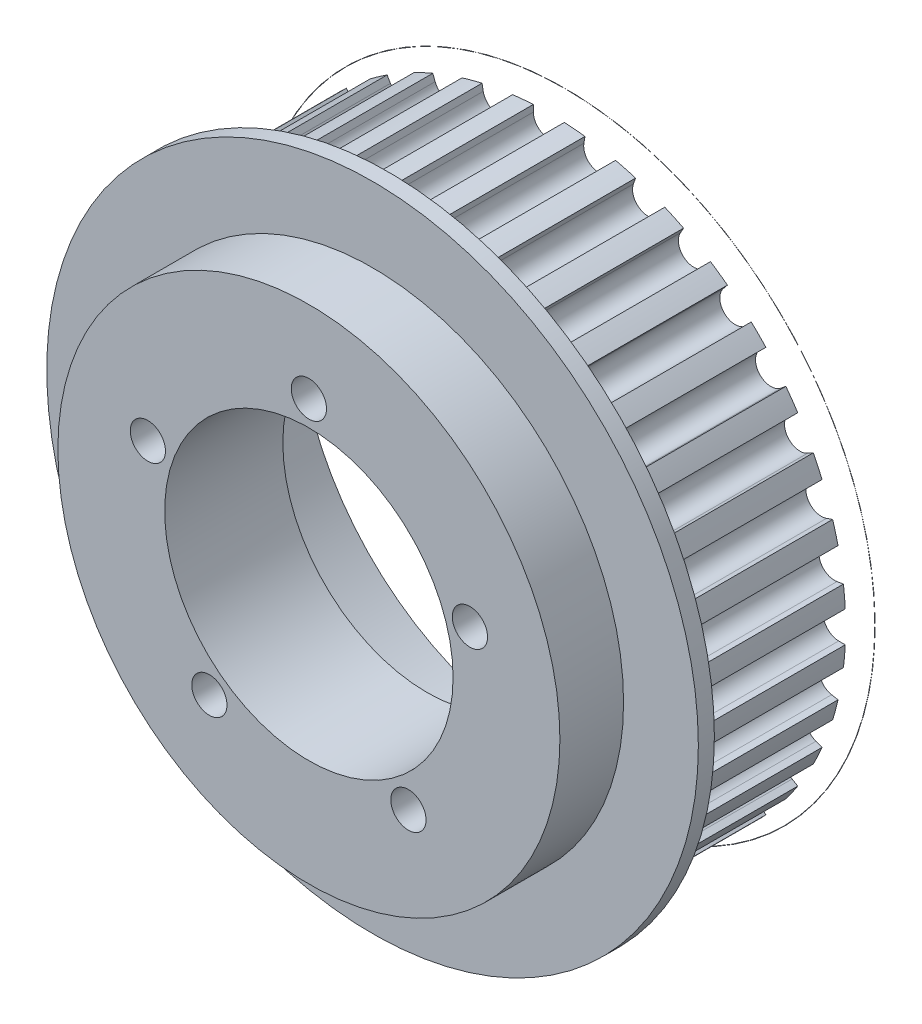
SolidWorks part; units mm, degrees
material "6061 Alloy"
ref_plane "Front Plane" through (0, 0, 0) normal (0, 0, 1) x (1, 0, 0)
ref_plane "Top Plane" through (0, 0, 0) normal (0, 1, 0) x (1, 0, 0)
ref_plane "Right Plane" through (0, 0, 0) normal (1, 0, 0) x (0, 0, -1)
sketch "Sketch1" plane through (0, 0, 0) normal (0, 0, 1) x (1, 0, 0)
  line L3 (-1.4732, 29.5146) -> (1.4732, 29.5146) construction
  line L4 (0, 0) -> (0, 25.7046) construction
  line L5 (0, 25.7046) -> (0, 27.7874) construction
  line L6 (-1.4479, 27.1372) -> (-1.4732, 29.5146)
  line L7 (1.4479, 27.1372) -> (1.4732, 29.5146)
  line L8 (0, 27.7874) -> (0, 29.5146) construction
  circle A0 centre (0, 0) radius 28.651 construction
  circle A1 centre (0, 0) radius 30.23 construction
  arc A3 (-1.4479, 27.1372) -> (1.4479, 27.1372) centre (0, 27.1526) ccw
  point P11 (0, 28.651)
  point P13 (0, 30.23)
  dimension "D3" = 1.448
  dimension "D1" = 2.9464
  dimension "D2" = 3.81
sketch "Sketch2" plane through (0, 0, 0) normal (1, 0, 0) x (0, 0, -1)
  line L0 (-17.02, 6.75) -> (17.02, 6.75)
  line L2 (-4.32, 22.86) -> (-17.02, 22.86)
  line L4 (-4.32, 30.23) -> (17.02, 30.23) construction
  line L5 (6.35, 30.23) -> (6.35, 27.7874) construction
  line L6 (-1.905, 27.7874) -> (14.605, 27.7874)
  line L7 (14.605, 27.7874) -> (14.605, 29.0087)
  line L8 (14.605, 29.0087) -> (14.605, 30.23) construction
  line L9 (17.02, 30.23) -> (17.02, 6.75)
  line L10 (-17.02, 0) -> (17.02, 0) construction
  line L11 (-17.02, 22.86) -> (-17.02, 6.75)
  line L12 (-4.32, 22.86) -> (-4.32, 30.23)
  line L13 (17.02, 30.23) -> (15.8125, 30.23)
  line L14 (15.8125, 30.23) -> (14.605, 30.23) construction
  line L15 (-1.905, 27.7874) -> (-1.905, 29.0087)
  line L16 (-1.905, 29.0087) -> (-1.905, 30.23) construction
  line L17 (-1.905, 30.23) -> (-3.1125, 30.23) construction
  line L18 (-3.1125, 30.23) -> (-4.32, 30.23)
  arc A0 (15.8125, 30.23) -> (14.605, 29.0087) centre (15.8125, 29.0224) ccw
  arc A1 (-1.905, 29.0087) -> (-3.1125, 30.23) centre (-3.1264, 29.0087) ccw
  point P25 (17.02, 0)
  point P26 (-4.32, 0)
  dimension "ID" = 13.5
  dimension "Hub Dia" = 45.72
  dimension "Outside Width" = 21.34
  dimension "Inside Width" = 16.51
  dimension "D2" = 60.46
revolve "Revolve1" add sketch "Sketch2" angle 360 mid plane about L10
sketch "Sketch3" plane through (0, 0, 0) normal (0, 0, 1) x (1, 0, 0)
  line L3 (-1.4479, 27.1372) -> (-1.4732, 29.5146) construction
  line L4 (1.4479, 27.1372) -> (1.4732, 29.5146) construction
  line L5 (-1.4479, 27.1372) -> (-1.4544, 27.7493)
  line L6 (1.4479, 27.1372) -> (1.4544, 27.7493)
  circle A2 centre (0, 0) radius 27.7874 construction
  arc A3 (-1.4479, 27.1372) -> (1.4479, 27.1372) centre (0, 27.1526) ccw construction
  arc A4 (-1.4479, 27.1372) -> (1.4479, 27.1372) centre (0, 27.1526) ccw
  arc A5 (1.4544, 27.7493) -> (-1.4544, 27.7493) centre (0, 0) ccw
extrude "Cut-Extrude1" cut sketch "Sketch3" against normal up to vertex (14.605 mm away) from vertex at 1.905 starting at point (0, 27.7874, 1.905)
pattern_circular "CirPattern1" count 36 over 360 about axis through (0, 0, 0) along (0, 0, 1) of "Cut-Extrude1"
sketch "Sketch4" plane through (0, 0, 0) normal (1, 0, 0) x (0, 0, -1)
  line L0 (15.8125, -30.23) -> (17.02, -30.23) construction
  line L1 (17.02, 30.23) -> (14.605, 30.23)
  line L2 (17.02, 30.23) -> (17.02, -30.23)
  line L3 (17.02, -30.23) -> (14.605, -30.23)
  line L4 (14.605, 30.23) -> (14.605, -30.23)
  line L5 (17.02, -30.23) -> (17.02, 30.23) construction
  line L6 (14.605, 29.0087) -> (14.605, -29.0087) construction
  line L7 (-4.32, 30.23) -> (-4.32, -30.23) construction
  line L8 (-4.32, 30.23) -> (-1.905, 30.23)
  line L9 (-4.32, 30.23) -> (-4.32, -30.23)
  line L10 (-4.32, -30.23) -> (-1.905, -30.23)
  line L11 (-1.905, 30.23) -> (-1.905, -30.23)
  line L12 (-1.905, -23.3044) -> (-1.905, -22.1921) construction
  line L13 (-17.02, 22.86) -> (-17.02, -22.86) construction
  line L14 (-17.02, 22.86) -> (-4.32, 22.86)
  line L15 (-17.02, 22.86) -> (-17.02, -22.86)
  line L16 (-17.02, -22.86) -> (-4.32, -22.86)
  line L17 (-4.32, 22.86) -> (-4.32, -22.86)
  line L18 (-4.32, 22.86) -> (-4.32, -22.86) construction
  line L19 (0, 0) -> (-17.02, 0) construction
  line L20 (-17.02, 0) -> (17.02, 0)
  dimension "D1" = 45.72
revolve "Cut-Revolve2" cut sketch "Sketch4" angle 360 about L19
sketch "Sketch5" plane through (0, 0, -14.605) normal (0, 0, -1) x (-1, 0, 0)
  line L72 (26.4735, 6.1382) -> (27.0752, 6.2509)
  line L73 (26.5733, 8.1241) -> (25.9958, 7.9209)
  line L74 (25.0054, 10.6421) -> (25.5784, 10.8575)
  line L75 (24.7588, 12.6151) -> (24.2255, 12.3147)
  line L76 (22.7775, 14.8225) -> (23.3044, 15.1342)
  line L77 (22.1921, 16.7228) -> (21.719, 16.3343)
  line L78 (19.8576, 18.5526) -> (20.3223, 18.9511)
  line L79 (18.9511, 20.3223) -> (18.5526, 19.8576)
  line L80 (16.3343, 21.719) -> (16.7228, 22.1921)
  line L81 (15.1342, 23.3044) -> (14.8225, 22.7775)
  line L82 (12.3147, 24.2255) -> (12.6151, 24.7588)
  line L83 (10.8575, 25.5784) -> (10.6421, 25.0054)
  line L84 (7.9209, 25.9958) -> (8.1241, 26.5733)
  line L85 (6.2509, 27.0752) -> (6.1382, 26.4735)
  line L86 (3.2864, 26.9764) -> (3.3863, 27.5803)
  line L87 (1.4544, 27.7493) -> (1.4479, 27.1372)
  line L88 (-1.4479, 27.1372) -> (-1.4544, 27.7493)
  line L89 (-3.3863, 27.5803) -> (-3.2864, 26.9764)
  line L90 (-6.1382, 26.4735) -> (-6.2509, 27.0752)
  line L91 (-8.1241, 26.5733) -> (-7.9209, 25.9958)
  line L92 (-10.6421, 25.0054) -> (-10.8575, 25.5784)
  line L93 (-12.6151, 24.7588) -> (-12.3147, 24.2255)
  line L94 (-14.8225, 22.7775) -> (-15.1342, 23.3044)
  line L95 (-16.7228, 22.1921) -> (-16.3343, 21.719)
  line L96 (-18.5526, 19.8576) -> (-18.9511, 20.3223)
  line L97 (-20.3223, 18.9511) -> (-19.8576, 18.5526)
  line L98 (-21.719, 16.3343) -> (-22.1921, 16.7228)
  line L99 (-23.3044, 15.1342) -> (-22.7775, 14.8225)
  line L100 (-24.2255, 12.3147) -> (-24.7588, 12.6151)
  line L101 (-25.5784, 10.8575) -> (-25.0054, 10.6421)
  line L102 (-25.9958, 7.9209) -> (-26.5733, 8.1241)
  line L103 (-27.0752, 6.2509) -> (-26.4735, 6.1382)
  line L104 (-26.9764, 3.2864) -> (-27.5803, 3.3863)
  line L105 (-27.7493, 1.4544) -> (-27.1372, 1.4479)
  line L106 (-27.1372, -1.4479) -> (-27.7493, -1.4544)
  line L107 (-27.5803, -3.3863) -> (-26.9764, -3.2864)
  line L108 (-26.4735, -6.1382) -> (-27.0752, -6.2509)
  line L109 (-26.5733, -8.1241) -> (-25.9958, -7.9209)
  line L110 (-25.0054, -10.6421) -> (-25.5784, -10.8575)
  line L111 (-24.7588, -12.6151) -> (-24.2255, -12.3147)
  line L112 (-22.7775, -14.8225) -> (-23.3044, -15.1342)
  line L113 (-22.1921, -16.7228) -> (-21.719, -16.3343)
  line L114 (-19.8576, -18.5526) -> (-20.3223, -18.9511)
  line L115 (-18.9511, -20.3223) -> (-18.5526, -19.8576)
  line L116 (-16.3343, -21.719) -> (-16.7228, -22.1921)
  line L117 (-15.1342, -23.3044) -> (-14.8225, -22.7775)
  line L118 (-12.3147, -24.2255) -> (-12.6151, -24.7588)
  line L119 (-10.8575, -25.5784) -> (-10.6421, -25.0054)
  line L120 (-7.9209, -25.9958) -> (-8.1241, -26.5733)
  line L121 (-6.2509, -27.0752) -> (-6.1382, -26.4735)
  line L122 (-3.2864, -26.9764) -> (-3.3863, -27.5803)
  line L123 (-1.4544, -27.7493) -> (-1.4479, -27.1372)
  line L124 (1.4479, -27.1372) -> (1.4544, -27.7493)
  line L125 (3.3863, -27.5803) -> (3.2864, -26.9764)
  line L126 (6.1382, -26.4735) -> (6.2509, -27.0752)
  line L127 (8.1241, -26.5733) -> (7.9209, -25.9958)
  line L128 (10.6421, -25.0054) -> (10.8575, -25.5784)
  line L129 (12.6151, -24.7588) -> (12.3147, -24.2255)
  line L130 (14.8225, -22.7775) -> (15.1342, -23.3044)
  line L131 (16.7228, -22.1921) -> (16.3343, -21.719)
  line L132 (18.5526, -19.8576) -> (18.9511, -20.3223)
  line L133 (20.3223, -18.9511) -> (19.8576, -18.5526)
  line L134 (21.719, -16.3343) -> (22.1921, -16.7228)
  line L135 (23.3044, -15.1342) -> (22.7775, -14.8225)
  line L136 (24.2255, -12.3147) -> (24.7588, -12.6151)
  line L137 (25.5784, -10.8575) -> (25.0054, -10.6421)
  line L138 (25.9958, -7.9209) -> (26.5733, -8.1241)
  line L139 (27.0752, -6.2509) -> (26.4735, -6.1382)
  line L140 (26.9764, -3.2864) -> (27.5803, -3.3863)
  line L141 (27.7493, -1.4544) -> (27.1372, -1.4479)
  line L142 (27.1372, 1.4479) -> (27.7493, 1.4544)
  line L143 (27.5803, 3.3863) -> (26.9764, 3.2864)
  line L144 (26.4735, 6.1382) -> (27.0752, 6.2509)
  line L145 (26.5733, 8.1241) -> (25.9958, 7.9209)
  line L146 (25.0054, 10.6421) -> (25.5784, 10.8575)
  line L147 (24.7588, 12.6151) -> (24.2255, 12.3147)
  line L148 (22.7775, 14.8225) -> (23.3044, 15.1342)
  line L149 (22.1921, 16.7228) -> (21.719, 16.3343)
  line L150 (19.8576, 18.5526) -> (20.3223, 18.9511)
  line L151 (18.9511, 20.3223) -> (18.5526, 19.8576)
  line L152 (16.3343, 21.719) -> (16.7228, 22.1921)
  line L153 (15.1342, 23.3044) -> (14.8225, 22.7775)
  line L154 (12.3147, 24.2255) -> (12.6151, 24.7588)
  line L155 (10.8575, 25.5784) -> (10.6421, 25.0054)
  line L156 (7.9209, 25.9958) -> (8.1241, 26.5733)
  line L157 (6.2509, 27.0752) -> (6.1382, 26.4735)
  line L158 (3.2864, 26.9764) -> (3.3863, 27.5803)
  line L159 (1.4544, 27.7493) -> (1.4479, 27.1372)
  line L160 (-1.4479, 27.1372) -> (-1.4544, 27.7493)
  line L161 (-3.3863, 27.5803) -> (-3.2864, 26.9764)
  line L162 (-6.1382, 26.4735) -> (-6.2509, 27.0752)
  line L163 (-8.1241, 26.5733) -> (-7.9209, 25.9958)
  line L164 (-10.6421, 25.0054) -> (-10.8575, 25.5784)
  line L165 (-12.6151, 24.7588) -> (-12.3147, 24.2255)
  line L166 (-14.8225, 22.7775) -> (-15.1342, 23.3044)
  line L167 (-16.7228, 22.1921) -> (-16.3343, 21.719)
  line L168 (-18.5526, 19.8576) -> (-18.9511, 20.3223)
  line L169 (-20.3223, 18.9511) -> (-19.8576, 18.5526)
  line L170 (-21.719, 16.3343) -> (-22.1921, 16.7228)
  line L171 (-23.3044, 15.1342) -> (-22.7775, 14.8225)
  line L172 (-24.2255, 12.3147) -> (-24.7588, 12.6151)
  line L173 (-25.5784, 10.8575) -> (-25.0054, 10.6421)
  line L174 (-25.9958, 7.9209) -> (-26.5733, 8.1241)
  line L175 (-27.0752, 6.2509) -> (-26.4735, 6.1382)
  line L176 (-26.9764, 3.2864) -> (-27.5803, 3.3863)
  line L177 (-27.7493, 1.4544) -> (-27.1372, 1.4479)
  line L178 (-27.1372, -1.4479) -> (-27.7493, -1.4544)
  line L179 (-27.5803, -3.3863) -> (-26.9764, -3.2864)
  line L180 (-26.4735, -6.1382) -> (-27.0752, -6.2509)
  line L181 (-26.5733, -8.1241) -> (-25.9958, -7.9209)
  line L182 (-25.0054, -10.6421) -> (-25.5784, -10.8575)
  line L183 (-24.7588, -12.6151) -> (-24.2255, -12.3147)
  line L184 (-22.7775, -14.8225) -> (-23.3044, -15.1342)
  line L185 (-22.1921, -16.7228) -> (-21.719, -16.3343)
  line L186 (-19.8576, -18.5526) -> (-20.3223, -18.9511)
  line L187 (-18.9511, -20.3223) -> (-18.5526, -19.8576)
  line L188 (-16.3343, -21.719) -> (-16.7228, -22.1921)
  line L189 (-15.1342, -23.3044) -> (-14.8225, -22.7775)
  line L190 (-12.3147, -24.2255) -> (-12.6151, -24.7588)
  line L191 (-10.8575, -25.5784) -> (-10.6421, -25.0054)
  line L192 (-7.9209, -25.9958) -> (-8.1241, -26.5733)
  line L193 (-6.2509, -27.0752) -> (-6.1382, -26.4735)
  line L194 (-3.2864, -26.9764) -> (-3.3863, -27.5803)
  line L195 (-1.4544, -27.7493) -> (-1.4479, -27.1372)
  line L196 (1.4479, -27.1372) -> (1.4544, -27.7493)
  line L197 (3.3863, -27.5803) -> (3.2864, -26.9764)
  line L198 (6.1382, -26.4735) -> (6.2509, -27.0752)
  line L199 (8.1241, -26.5733) -> (7.9209, -25.9958)
  line L200 (10.6421, -25.0054) -> (10.8575, -25.5784)
  line L201 (12.6151, -24.7588) -> (12.3147, -24.2255)
  line L202 (14.8225, -22.7775) -> (15.1342, -23.3044)
  line L203 (16.7228, -22.1921) -> (16.3343, -21.719)
  line L204 (18.5526, -19.8576) -> (18.9511, -20.3223)
  line L205 (20.3223, -18.9511) -> (19.8576, -18.5526)
  line L206 (21.719, -16.3343) -> (22.1921, -16.7228)
  line L207 (23.3044, -15.1342) -> (22.7775, -14.8225)
  line L208 (24.2255, -12.3147) -> (24.7588, -12.6151)
  line L209 (25.5784, -10.8575) -> (25.0054, -10.6421)
  line L210 (25.9958, -7.9209) -> (26.5733, -8.1241)
  line L211 (27.0752, -6.2509) -> (26.4735, -6.1382)
  line L212 (26.9764, -3.2864) -> (27.5803, -3.3863)
  line L213 (27.7493, -1.4544) -> (27.1372, -1.4479)
  line L214 (27.1372, 1.4479) -> (27.7493, 1.4544)
  line L215 (27.5803, 3.3863) -> (26.9764, 3.2864)
  arc A72 (26.4735, 6.1382) -> (26.9764, 3.2864) centre (26.7401, 4.715) ccw
  arc A73 (27.0752, 6.2509) -> (26.5733, 8.1241) centre (0, 0) ccw
  arc A74 (25.0054, 10.6421) -> (25.9958, 7.9209) centre (25.5151, 9.2867) ccw
  arc A75 (25.5784, 10.8575) -> (24.7588, 12.6151) centre (0, 0) ccw
  arc A76 (22.7775, 14.8225) -> (24.2255, 12.3147) centre (23.5148, 13.5763) ccw
  arc A77 (23.3044, 15.1342) -> (22.1921, 16.7228) centre (0, 0) ccw
  arc A78 (19.8576, 18.5526) -> (21.719, 16.3343) centre (20.8001, 17.4534) ccw
  arc A79 (20.3223, 18.9511) -> (18.9511, 20.3223) centre (0, 0) ccw
  arc A80 (16.3343, 21.719) -> (18.5526, 19.8576) centre (17.4534, 20.8001) ccw
  arc A81 (16.7228, 22.1921) -> (15.1342, 23.3044) centre (0, 0) ccw
  arc A82 (12.3147, 24.2255) -> (14.8225, 22.7775) centre (13.5763, 23.5148) ccw
  arc A83 (12.6151, 24.7588) -> (10.8575, 25.5784) centre (0, 0) ccw
  arc A84 (7.9209, 25.9958) -> (10.6421, 25.0054) centre (9.2867, 25.5151) ccw
  arc A85 (8.1241, 26.5733) -> (6.2509, 27.0752) centre (0, 0) ccw
  arc A86 (3.2864, 26.9764) -> (6.1382, 26.4735) centre (4.715, 26.7401) ccw
  arc A87 (3.3863, 27.5803) -> (1.4544, 27.7493) centre (0, 0) ccw
  arc A88 (-1.4479, 27.1372) -> (1.4479, 27.1372) centre (0, 27.1526) ccw
  arc A89 (-1.4544, 27.7493) -> (-3.3863, 27.5803) centre (0, 0) ccw
  arc A90 (-6.1382, 26.4735) -> (-3.2864, 26.9764) centre (-4.715, 26.7401) ccw
  arc A91 (-6.2509, 27.0752) -> (-8.1241, 26.5733) centre (0, 0) ccw
  arc A92 (-10.6421, 25.0054) -> (-7.9209, 25.9958) centre (-9.2867, 25.5151) ccw
  arc A93 (-10.8575, 25.5784) -> (-12.6151, 24.7588) centre (0, 0) ccw
  arc A94 (-14.8225, 22.7775) -> (-12.3147, 24.2255) centre (-13.5763, 23.5148) ccw
  arc A95 (-15.1342, 23.3044) -> (-16.7228, 22.1921) centre (0, 0) ccw
  arc A96 (-18.5526, 19.8576) -> (-16.3343, 21.719) centre (-17.4534, 20.8001) ccw
  arc A97 (-18.9511, 20.3223) -> (-20.3223, 18.9511) centre (0, 0) ccw
  arc A98 (-21.719, 16.3343) -> (-19.8576, 18.5526) centre (-20.8001, 17.4534) ccw
  arc A99 (-22.1921, 16.7228) -> (-23.3044, 15.1342) centre (0, 0) ccw
  arc A100 (-24.2255, 12.3147) -> (-22.7775, 14.8225) centre (-23.5148, 13.5763) ccw
  arc A101 (-24.7588, 12.6151) -> (-25.5784, 10.8575) centre (0, 0) ccw
  arc A102 (-25.9958, 7.9209) -> (-25.0054, 10.6421) centre (-25.5151, 9.2867) ccw
  arc A103 (-26.5733, 8.1241) -> (-27.0752, 6.2509) centre (0, 0) ccw
  arc A104 (-26.9764, 3.2864) -> (-26.4735, 6.1382) centre (-26.7401, 4.715) ccw
  arc A105 (-27.5803, 3.3863) -> (-27.7493, 1.4544) centre (0, 0) ccw
  arc A106 (-27.1372, -1.4479) -> (-27.1372, 1.4479) centre (-27.1526, 0) ccw
  arc A107 (-27.7493, -1.4544) -> (-27.5803, -3.3863) centre (0, 0) ccw
  arc A108 (-26.4735, -6.1382) -> (-26.9764, -3.2864) centre (-26.7401, -4.715) ccw
  arc A109 (-27.0752, -6.2509) -> (-26.5733, -8.1241) centre (0, 0) ccw
  arc A110 (-25.0054, -10.6421) -> (-25.9958, -7.9209) centre (-25.5151, -9.2867) ccw
  arc A111 (-25.5784, -10.8575) -> (-24.7588, -12.6151) centre (0, 0) ccw
  arc A112 (-22.7775, -14.8225) -> (-24.2255, -12.3147) centre (-23.5148, -13.5763) ccw
  arc A113 (-23.3044, -15.1342) -> (-22.1921, -16.7228) centre (0, 0) ccw
  arc A114 (-19.8576, -18.5526) -> (-21.719, -16.3343) centre (-20.8001, -17.4534) ccw
  arc A115 (-20.3223, -18.9511) -> (-18.9511, -20.3223) centre (0, 0) ccw
  arc A116 (-16.3343, -21.719) -> (-18.5526, -19.8576) centre (-17.4534, -20.8001) ccw
  arc A117 (-16.7228, -22.1921) -> (-15.1342, -23.3044) centre (0, 0) ccw
  arc A118 (-12.3147, -24.2255) -> (-14.8225, -22.7775) centre (-13.5763, -23.5148) ccw
  arc A119 (-12.6151, -24.7588) -> (-10.8575, -25.5784) centre (0, 0) ccw
  arc A120 (-7.9209, -25.9958) -> (-10.6421, -25.0054) centre (-9.2867, -25.5151) ccw
  arc A121 (-8.1241, -26.5733) -> (-6.2509, -27.0752) centre (0, 0) ccw
  arc A122 (-3.2864, -26.9764) -> (-6.1382, -26.4735) centre (-4.715, -26.7401) ccw
  arc A123 (-3.3863, -27.5803) -> (-1.4544, -27.7493) centre (0, 0) ccw
  arc A124 (1.4479, -27.1372) -> (-1.4479, -27.1372) centre (0, -27.1526) ccw
  arc A125 (1.4544, -27.7493) -> (3.3863, -27.5803) centre (0, 0) ccw
  arc A126 (6.1382, -26.4735) -> (3.2864, -26.9764) centre (4.715, -26.7401) ccw
  arc A127 (6.2509, -27.0752) -> (8.1241, -26.5733) centre (0, 0) ccw
  arc A128 (10.6421, -25.0054) -> (7.9209, -25.9958) centre (9.2867, -25.5151) ccw
  arc A129 (10.8575, -25.5784) -> (12.6151, -24.7588) centre (0, 0) ccw
  arc A130 (14.8225, -22.7775) -> (12.3147, -24.2255) centre (13.5763, -23.5148) ccw
  arc A131 (15.1342, -23.3044) -> (16.7228, -22.1921) centre (0, 0) ccw
  arc A132 (18.5526, -19.8576) -> (16.3343, -21.719) centre (17.4534, -20.8001) ccw
  arc A133 (18.9511, -20.3223) -> (20.3223, -18.9511) centre (0, 0) ccw
  arc A134 (21.719, -16.3343) -> (19.8576, -18.5526) centre (20.8001, -17.4534) ccw
  arc A135 (22.1921, -16.7228) -> (23.3044, -15.1342) centre (0, 0) ccw
  arc A136 (24.2255, -12.3147) -> (22.7775, -14.8225) centre (23.5148, -13.5763) ccw
  arc A137 (24.7588, -12.6151) -> (25.5784, -10.8575) centre (0, 0) ccw
  arc A138 (25.9958, -7.9209) -> (25.0054, -10.6421) centre (25.5151, -9.2867) ccw
  arc A139 (26.5733, -8.1241) -> (27.0752, -6.2509) centre (0, 0) ccw
  arc A140 (26.9764, -3.2864) -> (26.4735, -6.1382) centre (26.7401, -4.715) ccw
  arc A141 (27.5803, -3.3863) -> (27.7493, -1.4544) centre (0, 0) ccw
  arc A142 (27.1372, 1.4479) -> (27.1372, -1.4479) centre (27.1526, 0) ccw
  arc A143 (27.7493, 1.4544) -> (27.5803, 3.3863) centre (0, 0) ccw
  arc A144 (26.4735, 6.1382) -> (26.9764, 3.2864) centre (26.7401, 4.715) ccw
  arc A145 (27.0752, 6.2509) -> (26.5733, 8.1241) centre (0, 0) ccw
  arc A146 (25.0054, 10.6421) -> (25.9958, 7.9209) centre (25.5151, 9.2867) ccw
  arc A147 (25.5784, 10.8575) -> (24.7588, 12.6151) centre (0, 0) ccw
  arc A148 (22.7775, 14.8225) -> (24.2255, 12.3147) centre (23.5148, 13.5763) ccw
  arc A149 (23.3044, 15.1342) -> (22.1921, 16.7228) centre (0, 0) ccw
  arc A150 (19.8576, 18.5526) -> (21.719, 16.3343) centre (20.8001, 17.4534) ccw
  arc A151 (20.3223, 18.9511) -> (18.9511, 20.3223) centre (0, 0) ccw
  arc A152 (16.3343, 21.719) -> (18.5526, 19.8576) centre (17.4534, 20.8001) ccw
  arc A153 (16.7228, 22.1921) -> (15.1342, 23.3044) centre (0, 0) ccw
  arc A154 (12.3147, 24.2255) -> (14.8225, 22.7775) centre (13.5763, 23.5148) ccw
  arc A155 (12.6151, 24.7588) -> (10.8575, 25.5784) centre (0, 0) ccw
  arc A156 (7.9209, 25.9958) -> (10.6421, 25.0054) centre (9.2867, 25.5151) ccw
  arc A157 (8.1241, 26.5733) -> (6.2509, 27.0752) centre (0, 0) ccw
  arc A158 (3.2864, 26.9764) -> (6.1382, 26.4735) centre (4.715, 26.7401) ccw
  arc A159 (3.3863, 27.5803) -> (1.4544, 27.7493) centre (0, 0) ccw
  arc A160 (-1.4479, 27.1372) -> (1.4479, 27.1372) centre (0, 27.1526) ccw
  arc A161 (-1.4544, 27.7493) -> (-3.3863, 27.5803) centre (0, 0) ccw
  arc A162 (-6.1382, 26.4735) -> (-3.2864, 26.9764) centre (-4.715, 26.7401) ccw
  arc A163 (-6.2509, 27.0752) -> (-8.1241, 26.5733) centre (0, 0) ccw
  arc A164 (-10.6421, 25.0054) -> (-7.9209, 25.9958) centre (-9.2867, 25.5151) ccw
  arc A165 (-10.8575, 25.5784) -> (-12.6151, 24.7588) centre (0, 0) ccw
  arc A166 (-14.8225, 22.7775) -> (-12.3147, 24.2255) centre (-13.5763, 23.5148) ccw
  arc A167 (-15.1342, 23.3044) -> (-16.7228, 22.1921) centre (0, 0) ccw
  arc A168 (-18.5526, 19.8576) -> (-16.3343, 21.719) centre (-17.4534, 20.8001) ccw
  arc A169 (-18.9511, 20.3223) -> (-20.3223, 18.9511) centre (0, 0) ccw
  arc A170 (-21.719, 16.3343) -> (-19.8576, 18.5526) centre (-20.8001, 17.4534) ccw
  arc A171 (-22.1921, 16.7228) -> (-23.3044, 15.1342) centre (0, 0) ccw
  arc A172 (-24.2255, 12.3147) -> (-22.7775, 14.8225) centre (-23.5148, 13.5763) ccw
  arc A173 (-24.7588, 12.6151) -> (-25.5784, 10.8575) centre (0, 0) ccw
  arc A174 (-25.9958, 7.9209) -> (-25.0054, 10.6421) centre (-25.5151, 9.2867) ccw
  arc A175 (-26.5733, 8.1241) -> (-27.0752, 6.2509) centre (0, 0) ccw
  arc A176 (-26.9764, 3.2864) -> (-26.4735, 6.1382) centre (-26.7401, 4.715) ccw
  arc A177 (-27.5803, 3.3863) -> (-27.7493, 1.4544) centre (0, 0) ccw
  arc A178 (-27.1372, -1.4479) -> (-27.1372, 1.4479) centre (-27.1526, 0) ccw
  arc A179 (-27.7493, -1.4544) -> (-27.5803, -3.3863) centre (0, 0) ccw
  arc A180 (-26.4735, -6.1382) -> (-26.9764, -3.2864) centre (-26.7401, -4.715) ccw
  arc A181 (-27.0752, -6.2509) -> (-26.5733, -8.1241) centre (0, 0) ccw
  arc A182 (-25.0054, -10.6421) -> (-25.9958, -7.9209) centre (-25.5151, -9.2867) ccw
  arc A183 (-25.5784, -10.8575) -> (-24.7588, -12.6151) centre (0, 0) ccw
  arc A184 (-22.7775, -14.8225) -> (-24.2255, -12.3147) centre (-23.5148, -13.5763) ccw
  arc A185 (-23.3044, -15.1342) -> (-22.1921, -16.7228) centre (0, 0) ccw
  arc A186 (-19.8576, -18.5526) -> (-21.719, -16.3343) centre (-20.8001, -17.4534) ccw
  arc A187 (-20.3223, -18.9511) -> (-18.9511, -20.3223) centre (0, 0) ccw
  arc A188 (-16.3343, -21.719) -> (-18.5526, -19.8576) centre (-17.4534, -20.8001) ccw
  arc A189 (-16.7228, -22.1921) -> (-15.1342, -23.3044) centre (0, 0) ccw
  arc A190 (-12.3147, -24.2255) -> (-14.8225, -22.7775) centre (-13.5763, -23.5148) ccw
  arc A191 (-12.6151, -24.7588) -> (-10.8575, -25.5784) centre (0, 0) ccw
  arc A192 (-7.9209, -25.9958) -> (-10.6421, -25.0054) centre (-9.2867, -25.5151) ccw
  arc A193 (-8.1241, -26.5733) -> (-6.2509, -27.0752) centre (0, 0) ccw
  arc A194 (-3.2864, -26.9764) -> (-6.1382, -26.4735) centre (-4.715, -26.7401) ccw
  arc A195 (-3.3863, -27.5803) -> (-1.4544, -27.7493) centre (0, 0) ccw
  arc A196 (1.4479, -27.1372) -> (-1.4479, -27.1372) centre (0, -27.1526) ccw
  arc A197 (1.4544, -27.7493) -> (3.3863, -27.5803) centre (0, 0) ccw
  arc A198 (6.1382, -26.4735) -> (3.2864, -26.9764) centre (4.715, -26.7401) ccw
  arc A199 (6.2509, -27.0752) -> (8.1241, -26.5733) centre (0, 0) ccw
  arc A200 (10.6421, -25.0054) -> (7.9209, -25.9958) centre (9.2867, -25.5151) ccw
  arc A201 (10.8575, -25.5784) -> (12.6151, -24.7588) centre (0, 0) ccw
  arc A202 (14.8225, -22.7775) -> (12.3147, -24.2255) centre (13.5763, -23.5148) ccw
  arc A203 (15.1342, -23.3044) -> (16.7228, -22.1921) centre (0, 0) ccw
  arc A204 (18.5526, -19.8576) -> (16.3343, -21.719) centre (17.4534, -20.8001) ccw
  arc A205 (18.9511, -20.3223) -> (20.3223, -18.9511) centre (0, 0) ccw
  arc A206 (21.719, -16.3343) -> (19.8576, -18.5526) centre (20.8001, -17.4534) ccw
  arc A207 (22.1921, -16.7228) -> (23.3044, -15.1342) centre (0, 0) ccw
  arc A208 (24.2255, -12.3147) -> (22.7775, -14.8225) centre (23.5148, -13.5763) ccw
  arc A209 (24.7588, -12.6151) -> (25.5784, -10.8575) centre (0, 0) ccw
  arc A210 (25.9958, -7.9209) -> (25.0054, -10.6421) centre (25.5151, -9.2867) ccw
  arc A211 (26.5733, -8.1241) -> (27.0752, -6.2509) centre (0, 0) ccw
  arc A212 (26.9764, -3.2864) -> (26.4735, -6.1382) centre (26.7401, -4.715) ccw
  arc A213 (27.5803, -3.3863) -> (27.7493, -1.4544) centre (0, 0) ccw
  arc A214 (27.1372, 1.4479) -> (27.1372, -1.4479) centre (27.1526, 0) ccw
  arc A215 (27.7493, 1.4544) -> (27.5803, 3.3863) centre (0, 0) ccw
  dimension "D1" = 0
extrude "Cut-Extrude2" cut sketch "Sketch5" against normal offset from surface (1.51 mm away) 15 up to face at (0, 0, 1.905)
sketch "Sketch6" plane through (0, 0, -13.095) normal (0, 0, -1) x (-1, 0, 0)
  circle A0 centre (0, 0) radius 23.5
  dimension "D1" = 47
extrude "Cut-Extrude3" cut sketch "Sketch6" against normal blind 11.4
sketch "Sketch7" plane through (0, 0, 1.905) normal (0, 0, 1) x (1, 0, 0)
  circle A0 centre (0, 0) radius 13.5
  dimension "D1" = 27
extrude "Cut-Extrude4" cut sketch "Sketch7" against normal up to next (3.6 mm away)
sketch "Sketch8" plane through (0, 0, 1.905) normal (0, 0, 1) x (1, 0, 0)
  circle A0 centre (0, 0) radius 23.5
  circle A1 centre (0, 0) radius 13.5 construction
  circle A2 centre (0, 0) radius 13.5
  dimension "D1" = 47
extrude "Boss-Extrude1" add sketch "Sketch8" along normal blind 7.46
hole_wizard "M4 Tapped Hole1" positions "Sketch9" profile "Sketch10" tap size "M4" standard "ISO"
sketch "Sketch9" plane through (0, 0, 9.365) normal (0, 0, 1) x (1, 0, 0)
  circle A0 centre (0, 0) radius 15.85 construction
  point P0 (0, 15.85)
  point P24 (15.0742, 4.8979)
  point P25 (9.3164, -12.8229)
  point P26 (-9.3164, -12.8229)
  point P27 (-15.0742, 4.8979)
  point P28 (0, 0)
  dimension "D1" = 31.7
  dimension "D2" = 5
sketch "Sketch10" plane through (0, 15.85, 9.365) normal (1, 0, 0) x (0, -1, 0)
  line L0 (0, 0) -> (0, 23.97)
  line L1 (0, 23.97) -> (1.65, 23.97)
  line L2 (1.65, 23.97) -> (1.65, 0)
  line L5 (1.65, 0) -> (0, 0)
  line L11 (0, -6.35) -> (0, 107.95) construction
  dimension "Thread Major Dia." = 3.3
  dimension "Thru Tap Drill Depth" = 23.97
sketch "Sketch11" plane through (0, 0, 1.905) normal (0, 0, 1) x (1, 0, 0)
  circle A0 centre (0, 0) radius 30.5
  circle A1 centre (0, 0) radius 23.5 construction
  circle A2 centre (0, 0) radius 23.5
  dimension "D1" = 61
extrude "Boss-Extrude3" add sketch "Sketch11" along normal blind 1.5
equation "\"D2@Sketch2\" =  \"OD@Sketch1\""
